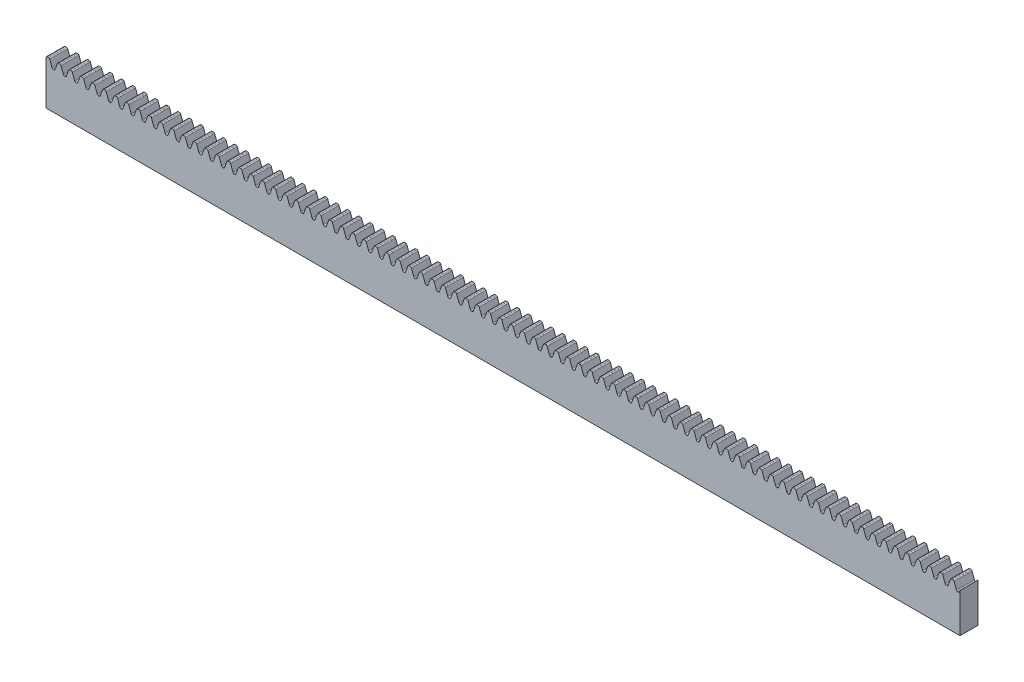
SolidWorks part; units mm, degrees
ref_plane "Front Plane" through (0, 0, 0) normal (0, 0, 1) x (1, 0, 0)
ref_plane "Top Plane" through (0, 0, 0) normal (0, 1, 0) x (1, 0, 0)
ref_plane "Right Plane" through (0, 0, 0) normal (1, 0, 0) x (0, 0, -1)
sketch "Sketch1" plane through (0, 0, 0) normal (0, 0, 1) x (1, 0, 0)
  line L0 (-150, 5) -> (-150, -5) construction
  line L1 (-150, -5) -> (150, -5) construction
  line L2 (150, -5) -> (150, 5) construction
  line L4 (0, 5) -> (0, -5) construction
  line L5 (-150, 4.2) -> (150, 4.2) construction
  line L6 (-148.6203, 5) -> (-147.946, 5) construction
  line L7 (-147.946, 5) -> (-147.2909, 3.2) construction
  line L8 (-148.6203, 5) -> (-149.2755, 3.2) construction
  line L9 (-149.2755, 3.2) -> (-147.2909, 3.2) construction
  line L10 (-148.2832, 5) -> (-148.2832, 3.2) construction
  line L11 (-150, 0) -> (-143.2566, 0) construction
  line L12 (150, 0) -> (143.2566, 0) construction
  point P15 (-145.7699, 5)
  point P16 (-59.5, -5)
  point P17 (-147.6549, 4.2)
  point P18 (-148.9115, 4.2)
  point P21 (-0.4, -5)
  dimension "Length" = 300
  dimension "Height" = 10
  dimension "Approximate Number of Teeth" = 119
  dimension "Pressure Angle" = 20
  dimension "Circular Pitch" = 2.5133
  dimension "Addendum" = 0.8
  dimension "Dedendum" = 1
  dimension "Circular Tooth Thickness" = 1.2566
  dimension "Module" = 0.8
  dimension "Rack Length" = 296.5663
  dimension "D1" = 5.0265
sketch "Sketch2" plane through (0, 0, 0) normal (1, 0, 0) x (0, 0, -1)
  line L0 (-2, 0) -> (2, 0) construction
  dimension "Face Width" = 4
sketch "Sketch3" plane through (0, 0, 0) normal (0, 0, 1) x (1, 0, 0)
  line L1 (-150, 5) -> (150, 5)
  line L2 (-150, 5) -> (-150, -5)
  line L3 (-150, -5) -> (150, -5)
  line L4 (150, 5) -> (150, -5)
extrude "Boss-Extrude1" add sketch "Sketch3" against normal up to vertex (2 mm away) and the other way up to vertex (2 mm away) up to point (0, 0, -2) other way up to point (0, 0, 2)
sketch "Sketch4" plane through (0, 0, 0) normal (0, 0, 1) x (1, 0, 0)
  line L0 (-148.2832, 5) -> (-145.7699, 5) construction
  line L9 (-147.0265, 5) -> (-147.0265, 3.2)
  line L10 (-147.0265, 3.2) -> (-147.2909, 3.2)
  line L11 (-147.2909, 3.2) -> (-147.946, 5)
  line L12 (-147.946, 5) -> (-147.0265, 5)
  line L13 (-148.6203, 5) -> (-149.2755, 3.2)
  line L14 (-149.2755, 3.2) -> (-149.5398, 3.2)
  line L15 (-149.5398, 3.2) -> (-149.5398, 5)
  line L16 (-149.5398, 5) -> (-148.6203, 5)
  line L17 (150, 5) -> (-150, 5) construction
  line L18 (-148.6203, 5) -> (-148.4324, 5)
  line L19 (-148.134, 5) -> (-147.946, 5)
  arc A0 (-149.4634, 3.2) -> (-149.2112, 3.3766) centre (-149.4634, 3.4684) ccw
  arc A1 (-147.3552, 3.3766) -> (-147.1029, 3.2) centre (-147.1029, 3.4684) ccw
  arc A2 (-148.6846, 4.8234) -> (-148.4324, 5) centre (-148.4324, 4.7316) cw
  arc A3 (-148.134, 5) -> (-147.8818, 4.8234) centre (-148.134, 4.7316) cw
  dimension "D1" = 0.2684
extrude "Cut-Extrude1" cut sketch "Sketch4" against normal through all both and the other way through all contours L14 A0 L13 L16 L15 | L13 A2 L18 | L19 A3 L11 | L11 A1 L10 L9 L12 region at (-147.3532, 4.2723, 0) region at (-147.9724, 4.9623, 0) region at (-148.5939, 4.9623, 0) region at (-149.2131, 4.2723, 0)
pattern_linear "LPattern1" count 120 spacing 2.5133 along (1, 0, 0) count 2 spacing 2.5133 along (-1, 0, 0) of "Cut-Extrude1"
sketch "Drawing Refernce 1" plane through (0, 0, 2) normal (0, 0, 1) x (1, 0, 0)
  line L0 (-150, 0) -> (150, 0) construction
  point P6 (-135, 0)
  point P7 (-127.5, 0)
  point P8 (135, 0)
  dimension "D1" = 15
  dimension "D2" = 22.5
  dimension "D3" = 15
sketch "Sketch5" plane through (0, 0, 2) normal (0, 0, 1) x (1, 0, 0)
  line L1 (-150, -5) -> (-53.2, -5)
  line L2 (-150, -5) -> (-150, 52.9559)
  line L3 (-150, 52.9559) -> (-53.2, 52.9559)
  line L4 (-53.2, -5) -> (-53.2, 52.9559)
  dimension "D1" = 96.8
extrude "Cut-Extrude2" cut sketch "Sketch5" against normal blind 10
equation "\"Diametral Pitch\"= 1 / \"Module\""
equation "\"Pressure Angle\"=20"
equation "\"Dedendum\"= 1.25 / \"Diametral Pitch\""
equation "\"Addendum\"= 1 / \"Diametral Pitch\""
equation "\"WorkingDepth\"= 2 / \"Diametral Pitch\""
equation "\"WholeDepth\"= 2.25 / \"Diametral Pitch\""
equation "\"Clearance\"= 0.25 / \"Diametral Pitch\""
equation "\"ToothThickness\"= ( pi / 2 ) / \"Diametral Pitch\""
equation "\"CircularPitch\"= pi / \"Diametral Pitch\""
equation "\"Fillet\"= \"Clearance\" * cos ( \"Pressure Angle\" ) * tan ( ( 90 + \"Pressure Angle\" ) / 2 )"
equation "\"Module\"= 0.8"
equation "\"Addendum@Sketch1\"=\"Addendum\""
equation "\"Pressure Angle@Sketch1\"=\"Pressure Angle\""
equation "\"Dedendum@Sketch1\"=\"Dedendum\""
equation "\"Circular Pitch@Sketch1\"=\"CircularPitch\""
equation "\"Circular Tooth Thickness@Sketch1\"=\"ToothThickness\""
equation "\"Module@Sketch1\"=\"Module\""
equation "\"Approximate Number of Teeth@Sketch1\" = int ( \"Length@Sketch1\" /  ( 2 * \"Circular Tooth Thickness@Sketch1\" )  ) "
equation "\"Rack Length@Sketch1\" = \"Circular Pitch@Sketch1\" *  ( \"Approximate Number of Teeth@Sketch1\" - 1 ) "
equation "\"D3@LPattern1\"=\"CircularPitch\""
equation "\"D1@LPattern1\"=\"Approximate Number of Teeth@Sketch1\"+1"
equation "\"D1@Sketch1\"=\"Circular Pitch@Sketch1\"*2"
equation "\"D1@Sketch4\"=\"Fillet\""
equation "\"D4@LPattern1\"=\"CircularPitch\""
equation "\"D2@Drawing Refernce 1\"=\"D1@Drawing Refernce 1\"*1.5"
equation "\"D3@Drawing Refernce 1\"=\"D1@Drawing Refernce 1\""
